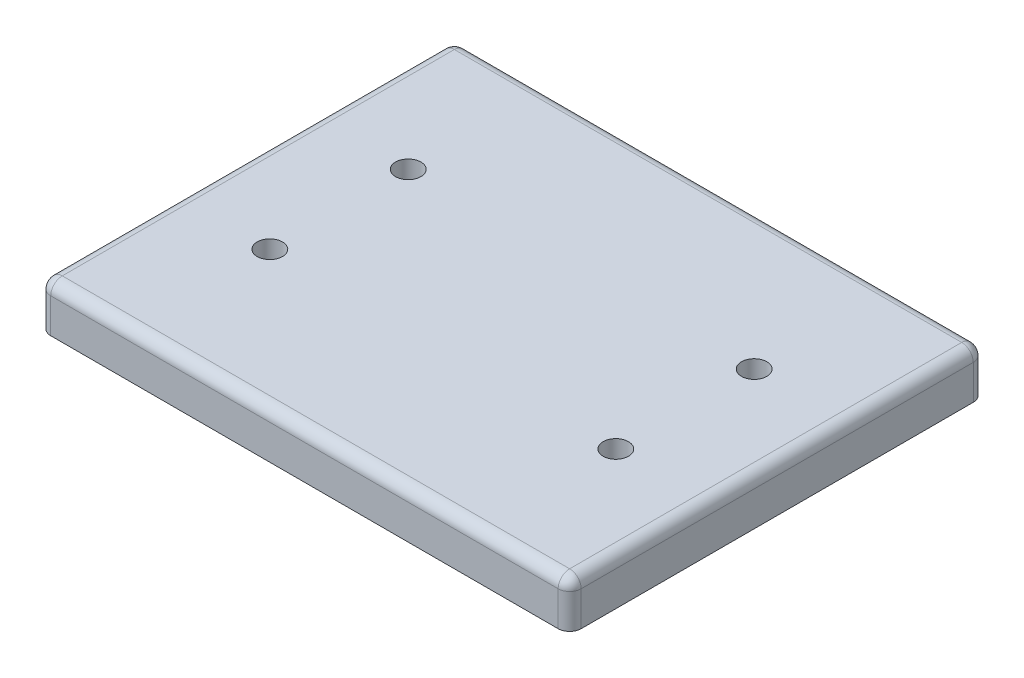
SolidWorks part; units mm, degrees
ref_plane "Front Plane" through (0, 0, 0) normal (0, 0, 1) x (1, 0, 0)
ref_plane "Top Plane" through (0, 0, 0) normal (0, 1, 0) x (1, 0, 0)
ref_plane "Right Plane" through (0, 0, 0) normal (1, 0, 0) x (0, 0, -1)
sketch "Sketch1" plane through (0, 0, 0) normal (0, 1, 0) x (1, 0, 0)
  line L1 (-115, 90) -> (115, 90)
  line L2 (-115, 90) -> (-115, -90)
  line L3 (-115, -90) -> (115, -90)
  line L4 (115, 90) -> (115, -90)
  line L5 (-115, 90) -> (115, -90) construction
  line L6 (-115, -90) -> (115, 90) construction
  point P0 (0, 0)
  dimension "D1" = 230
  dimension "D2" = 180
extrude "Boss-Extrude1" add sketch "Sketch1" along normal blind 20
fillet "Fillet1" radius 5 4 edges at (0, 20, 90) (-115, 20, 0) (0, 20, -90) (115, 20, 0)
sketch "Sketch2" plane through (0, 0, 0) normal (0, -1, 0) x (1, 0, 0)
  line L0 (-115, 0) -> (113.1459, 0) construction
  line L1 (-115, -90) -> (-115, 90) construction
  line L2 (0, 90) -> (0, -90) construction
  line L3 (-115, 90) -> (115, 90) construction
  line L4 (115, -90) -> (-115, -90) construction
  circle A0 centre (-75, 30) radius 9
  circle A1 centre (-75, 30) radius 5.5
  dimension "D1" = 18
  dimension "D4" = 11
  dimension "D2" = 75
  dimension "D3" = 30
extrude "Cut-Extrude1" cut sketch "Sketch2" against normal blind 10 contours A0
extrude "Cut-Extrude2" cut sketch "Sketch2<3>" against normal through all contours A1 region at (-75, 0, 30)
sketch "Sketch2<3>" plane through (0, 0, 0) normal (0, -1, 0) x (1, 0, 0) same geometry as "Sketch2"
mirror "Mirror1" about plane through (0, 0, 0) normal (1, 0, 0) of "Cut-Extrude1", "Cut-Extrude2"
mirror "Mirror2" about plane through (0, 0, 0) normal (0, 0, 1) of "Mirror1"
fillet "Fillet2" radius 5 8 edges at (113.5355, 18.5355, -88.5355) (-113.5355, 18.5355, -88.5355) (-113.5355, 18.5355, 88.5355) (113.5355, 18.5355, 88.5355) (115, 7.5, -90) (-115, 7.5, -90) (-115, 7.5, 90) (115, 7.5, 90)
